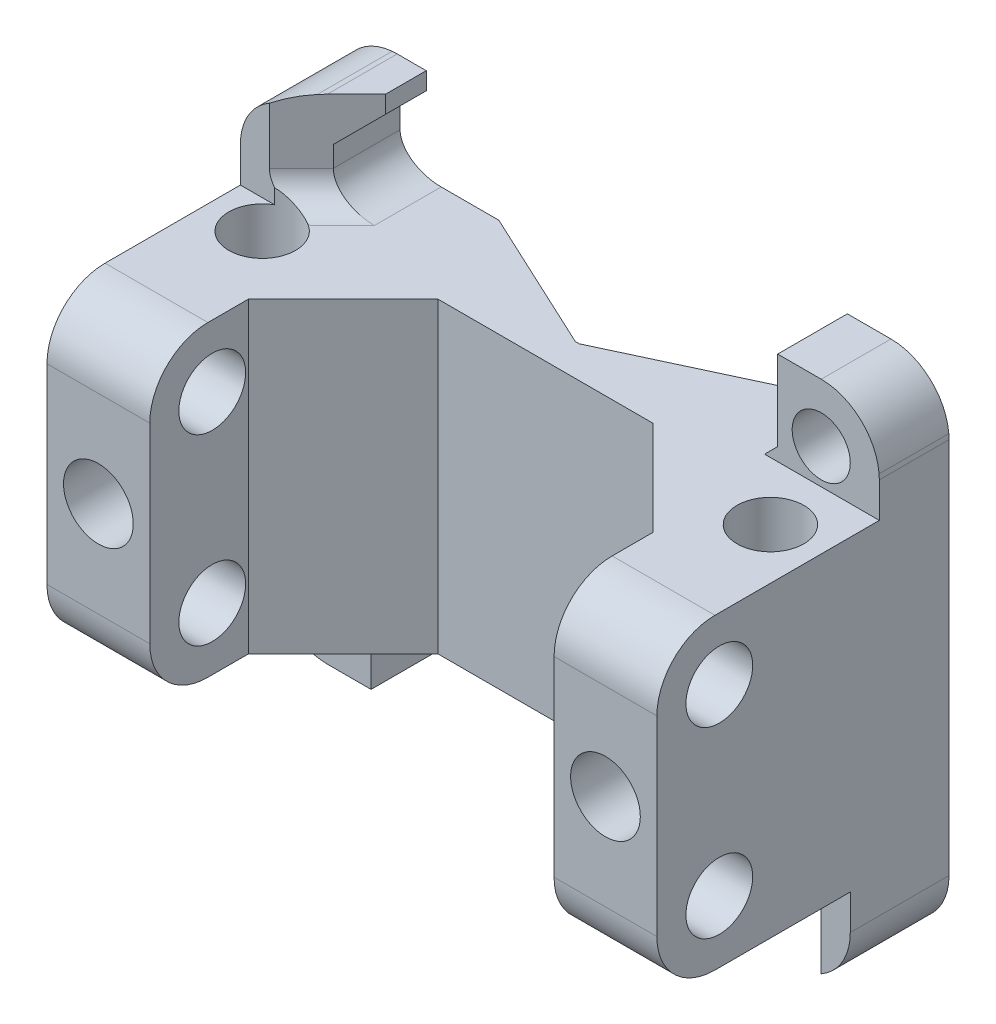
SolidWorks part; units mm, degrees
ref_plane "Top Plane" through (0, 0, 0) normal (0, 0, 1) x (1, 0, 0)
ref_plane "Right Plane" through (0, 0, 0) normal (0, 1, 0) x (1, 0, 0)
ref_plane "Front Plane" through (0, 0, 0) normal (1, 0, 0) x (0, 0, -1)
sketch "Sketch1" plane through (0, 0, 0) normal (0, 0, 1) x (1, 0, 0)
  line L0 (0.6, 14) -> (0.6, 3.577)
  line L3 (20.4, 3) -> (20.4, 13.79)
  line L7 (0, 15) -> (0, 2)
  line L8 (2, 0) -> (19, 0)
  line L9 (19, 0) -> (19.1743, 0.0076)
  line L10 (21, 2) -> (21, 15)
  line L11 (21, 15) -> (20.9924, 15.1743)
  line L12 (19, 17) -> (2, 17)
  line L13 (2, 17) -> (1.8257, 16.9924)
  line L14 (0, 15) -> (0, 2)
  line L15 (2, 0) -> (3.5, 0)
  line L16 (19, 0) -> (19.1743, 0.0076)
  line L17 (21, 2) -> (21, 15)
  line L18 (21, 15) -> (20.9924, 15.1743)
  line L19 (19, 17) -> (17.5, 17)
  line L20 (2, 17) -> (1.8257, 16.9924)
  line L21 (3.5, 0) -> (3.5, 3.577)
  line L22 (3.5, 3.577) -> (0.6, 3.577)
  line L23 (18, 0.6) -> (18, 0)
  line L24 (5.623, 4.077) -> (1.975, 4.077) construction
  line L25 (17.5, 17) -> (17.5, 13.79)
  line L26 (0.6, 15) -> (0.6, 2) construction
  line L27 (2, 0.6) -> (18.9869, 0.6) construction
  line L28 (17.5, 13.79) -> (20.4, 13.79)
  line L29 (19.45, 13.59) -> (19.15, 13.59) construction
  line L30 (20.4, 3) -> (18, 0.6)
  line L31 (20.4, 2) -> (20.4, 14.9869) construction
  line L32 (20.4, 14.9869) -> (20.3936, 15.1339) construction
  line L33 (19, 16.4) -> (2.0131, 16.4) construction
  line L34 (18.9869, 0.6) -> (19.1339, 0.6064) construction
  line L35 (20.4, 3) -> (20.4, 0.6) construction
  line L36 (20.4, 0.6) -> (18, 0.6) construction
  line L37 (2, 0) -> (19, 0) construction
  line L38 (18, 0) -> (19, 0)
  line L39 (20.4, 3) -> (21, 3) construction
  line L40 (2, 0) -> (19, 0) construction
  line L41 (3, 16.4) -> (0.6, 14)
  line L42 (0.6, 14) -> (0.6, 16.4) construction
  line L43 (0.6, 16.4) -> (3, 16.4) construction
  line L44 (3, 16.4) -> (3, 17)
  line L45 (2.0131, 16.4) -> (1.8661, 16.3936) construction
  line L46 (19, 17) -> (2, 17) construction
  line L47 (3, 17) -> (2, 17)
  line L48 (0.6, 14) -> (0, 14) construction
  line L49 (19, 17) -> (2, 17) construction
  arc A4 (0, 2) -> (2, 0) centre (2, 2) ccw
  arc A5 (19.1743, 0.0076) -> (21, 2) centre (19, 2) ccw
  arc A6 (20.9924, 15.1743) -> (19, 17) centre (19, 15) ccw
  arc A7 (1.8257, 16.9924) -> (0, 15) centre (2, 15) ccw
  arc A8 (0, 2) -> (2, 0) centre (2, 2) ccw
  arc A9 (19.1743, 0.0076) -> (21, 2) centre (19, 2) ccw
  arc A10 (20.9924, 15.1743) -> (19, 17) centre (19, 15) ccw
  arc A11 (1.8257, 16.9924) -> (0, 15) centre (2, 15) ccw
  circle A12 centre (2, 2) radius 1 construction
  arc A13 (0.6, 2) -> (2, 0.6) centre (2, 2) ccw construction
  circle A14 centre (19, 15) radius 1 construction
  arc A15 (20.3936, 15.1339) -> (19, 16.4) centre (19, 15) ccw construction
  circle A16 centre (19, 15) radius 1
  circle A17 centre (2, 2) radius 1
  arc A22 (19.1339, 0.6064) -> (20.4, 2) centre (19, 2) ccw construction
  arc A23 (1.8661, 16.3936) -> (0.6, 15) centre (2, 15) ccw construction
  point P42 (19.3, 13.59)
  dimension "D3" = 0.5
  dimension "D4" = 0.5
  dimension "D5" = 0.2
  dimension "D6" = 0.5
  dimension "D7" = 2.4
  dimension "D1" = 0
  dimension "D2" = 0.6
extrude "Boss-Extrude2" add sketch "Sketch1" along normal blind 2.4 contours L16 A9 L17 L18 A10 L19 L25 L28 L3 L30 L23 L38 | L14 A8 L15 L21 L22 L0 L41 L44 L47 L20 A11 | A17 | A16
sketch "Sketch2" plane through (0, 0, 2.4) normal (0, 0, 1) x (1, 0, 0)
  line L0 (3, 13.79) -> (21, 13.79)
  line L1 (18, 0) -> (18, 3.21)
  line L2 (3, 13.79) -> (3, 17)
  line L5 (0, 15) -> (0, 2) construction
  line L6 (18, 3.21) -> (0, 3.21)
  line L7 (0, 15) -> (0, 2)
  line L8 (2, 0) -> (19, 0)
  line L9 (19, 0) -> (19.1743, 0.0076)
  line L10 (21, 2) -> (21, 15)
  line L11 (21, 15) -> (20.9924, 15.1743)
  line L12 (19, 17) -> (2, 17)
  line L13 (2, 17) -> (1.8257, 16.9924)
  line L14 (0, 15) -> (0, 3.21)
  line L15 (18, 0) -> (19, 0)
  line L16 (19, 0) -> (19.1743, 0.0076)
  line L17 (21, 2) -> (21, 13.79)
  line L19 (3, 17) -> (2, 17)
  line L20 (2, 17) -> (1.8257, 16.9924)
  line L22 (17.5, 13.79) -> (20.4, 13.79) construction
  arc A4 (0, 2) -> (2, 0) centre (2, 2) ccw
  arc A5 (19.1743, 0.0076) -> (21, 2) centre (19, 2) ccw
  arc A6 (20.9924, 15.1743) -> (19, 17) centre (19, 15) ccw
  arc A7 (1.8257, 16.9924) -> (0, 15) centre (2, 15) ccw
  arc A9 (19.1743, 0.0076) -> (21, 2) centre (19, 2) ccw
  arc A11 (1.8257, 16.9924) -> (0, 15) centre (2, 15) ccw
  dimension "D1" = 0
extrude "Boss-Extrude5" add sketch "Sketch2" against normal blind 0.1 and the other way blind 1
chamfer "Chamfer1" distance 2 angle 45 2 edges at (18, 1.605, 3.4) (3, 15.395, 3.4)
fillet "Fillet1" radius 1 2 edges at (19.45, 3.21, 2.85) (1.55, 13.79, 2.85)
sketch "Sketch3" plane through (0, 13.79, 0) normal (0, 1, 0) x (1, 0, 0)
  line L0 (21, -3.4) -> (2.4142, -3.4) construction
  line L1 (21, -4.4) -> (17.5, -4.4) construction
  line L2 (21, -4.4) -> (21, -3.4)
  line L3 (21, -3.4) -> (19.8179, -3.4)
  line L4 (17.5, -4.4) -> (17.5, -3.4)
  line L5 (17.5, -2.4) -> (17.5, -3.4) construction
  line L6 (18.6821, -3.4) -> (17.5, -3.4)
  arc A0 (18.6821, -3.4) -> (19.8179, -3.4) centre (19.25, -4.4) ccw
  arc A1 (21, -4.4) -> (17.5, -4.4) centre (19.25, -4.4) cw
  dimension "D1" = 0.6
  dimension "D2" = 1
extrude "Boss-Extrude6" add sketch "Sketch3" against normal up to surface (10.58 mm away) up to face at (7.1786, 3.21, 2.7)
ref_plane "Plane1" through (10.5, 0, 0) normal (-1, 0, 0) x (0, 0, 1)
sketch "Sketch9" plane through (0, 13.79, 0) normal (0, 1, 0) x (1, 0, 0)
  circle A0 centre (19.25, -4.4) radius 1.15
  arc A1 (18.6821, -3.4) -> (19.8179, -3.4) centre (19.25, -4.4) ccw construction
extrude "Cut-Extrude5" cut sketch "Sketch9" against normal through all both and the other way through all
sketch "Sketch10" plane through (0, 13.79, 0) normal (0, 1, 0) x (1, 0, 0)
  line L1 (17.5, -6.6594) -> (17.5, -4.4)
  line L2 (17.5, -4.4) -> (18.1, -4.4)
  line L3 (20.4, -4.4) -> (21, -4.4)
  line L4 (21, -4.4) -> (21, -6.6594)
  line L5 (21, -6.6594) -> (17.5, -6.6594)
  circle A1 centre (19.25, -4.4) radius 1.15 construction
  arc A2 (18.1, -4.4) -> (20.4, -4.4) centre (19.25, -4.4) ccw
  dimension "D1" = 1.1094
extrude "Boss-Extrude10" add sketch "Sketch10" against normal up to surface (10.58 mm away) up to face at (13.2143, 3.21, 3.5417)
chamfer "Chamfer4" distance 3.3 angle 45 1 edges at (17.5, 8.5, 3.4)
sketch "Sketch12" plane through (21, 0, 0) normal (1, 0, 0) x (0, 0, -1)
  line L0 (-6.6594, 5.35) -> (-10.0594, 5.35) construction
  line L1 (-6.6594, 3.21) -> (-10.0594, 3.21)
  line L2 (-6.6594, 3.21) -> (-6.6594, 13.79)
  line L3 (-6.6594, 13.79) -> (-10.0594, 13.79)
  line L4 (-10.0594, 3.21) -> (-10.0594, 13.79)
  line L5 (-6.6594, 8.5) -> (-10.0594, 8.5) construction
  circle A0 centre (-7.9094, 5.35) radius 1.15
  circle A1 centre (-7.9094, 11.65) radius 1.15
  dimension "D1" = 2.3
  dimension "D2" = 1
  dimension "D4" = 4
  dimension "D3" = 0.1
extrude "Boss-Extrude11" add sketch "Sketch12" against normal blind 3.54
fillet "Fillet2" radius 2 2 edges at (19.23, 3.21, 10.0594) (19.23, 13.79, 10.0594)
sketch "Sketch13" plane through (0, 0, 10.0594) normal (0, 0, 1) x (1, 0, 0)
  line L0 (21, 8.5) -> (17.46, 8.5) construction
  line L1 (21, 11.79) -> (21, 5.21) construction
  line L2 (17.46, 11.79) -> (17.46, 5.21) construction
  circle A0 centre (19.23, 8.5) radius 1.2
  point P8 (19.23, 8.5)
  dimension "D1" = 2.4
extrude "Cut-Extrude7" cut sketch "Sketch13" against normal blind 5.5
mirror "Mirror1" about plane through (10.5, 0, 0) normal (-1, 0, 0) of "Cut-Extrude7", "Chamfer4", "Boss-Extrude6", "Cut-Extrude5", "Boss-Extrude10", "Boss-Extrude11", "Fillet2"
ref_plane "Plane2" through (0, 8.5, 0) normal (0, 1, 0) x (1, 0, 0)
chamfer "Chamfer3" distance 1 angle 45 2 edges at (20.4, 13.79, 1.15) (0.6, 3.577, 1.15)
sketch "Sketch6" plane through (0, 0, 2.3) normal (0, 0, -1) x (-1, 0, 0)
  line L0 (-3.5, 3.21) -> (-17.4858, 3.21) construction
  line L1 (0, 3.21) -> (-17.4858, 3.21)
  line L2 (0, 3.21) -> (0, 3.81)
  line L3 (0, 3.81) -> (-17.4858, 3.81)
  line L6 (-17.5, 13.79) -> (-3.5142, 13.79)
  line L7 (-21, 13.89) -> (-21, 13.19)
  line L8 (-21, 13.19) -> (-0.5, 13.19)
  line L9 (-0.5, 15.5) -> (-0.5, 13.19)
  line L12 (-10.5, 14.28) -> (-10.5, 13.79) construction
  line L13 (-4.1902, 14.28) -> (-16.8098, 14.28) construction
  line L14 (-21, 3.674) -> (-17.8, 3.674)
  line L18 (-20.4, 3) -> (-18.9, 1.5) construction
  line L19 (-20.4, 3) -> (-20.4, 12.79) construction
  line L20 (-17.4858, 3.21) -> (-17.4858, 3.81)
  line L22 (-21, 3.674) -> (-20.4, 3)
  line L23 (-18.9, 1.5) -> (-18.9, 2.21)
  line L24 (-2.1, 14.79) -> (-2.1, 15.5)
  line L25 (-2.1, 15.5) -> (-0.5, 15.5)
  line L26 (-17.5, 13.79) -> (-3.5142, 13.79) construction
  line L27 (-18.9, 1.5) -> (-20.4, 1.5)
  line L28 (-20.4, 1.5) -> (-20.4, 3)
  line L29 (-17.4858, 3.81) -> (-17.8, 3.674)
  line L30 (-17.924, 3.774) -> (-18.176, 3.774) construction
  line L31 (-17.9, 3.774) -> (-17.9, 4.426) construction
  line L32 (0, 15) -> (0, 2) construction
  line L33 (-21, 2) -> (-21, 15) construction
  line L34 (-17.5, 13.79) -> (-17.5, 13.89)
  line L35 (-17.5, 17) -> (-17.5, 13.79) construction
  line L36 (-17.5, 13.89) -> (-21, 13.89)
  line L39 (-10.5, 13.79) -> (-10.5, 13.19) construction
  line L40 (-11.5185, 3.21) -> (-11.5185, 3.81) construction
  line L41 (-0.6, 14) -> (-0.6, 4.577) construction
  arc A0 (-18.9, 2.21) -> (-17.4858, 3.21) centre (-17.8393, 2.21) cw
  ellipse E0 centre (-17.4858, 2.21) end of major axis (-18.9, 2.21) minor radius 1 (-17.4858, 3.21) -> (-18.9, 2.21) ccw construction
  ellipse E1 centre (-3.5142, 14.79) end of major axis (-2.1, 14.79) minor radius 1 (-3.5142, 13.79) -> (-2.1, 14.79) ccw construction
  ellipse E2 centre (-3.5142, 14.79) end of major axis (-2.1, 14.79) minor radius 1 (-3.5142, 13.79) -> (-2.1, 14.79) ccw
  line M19 (-17.5, 13.79) -> (-19.4, 13.79)
  line M20 (-19.4, 13.79) -> (-20.4, 12.79)
  line M21 (-20.4, 12.79) -> (-20.4, 3)
  line M22 (-20.4, 3) -> (-18.9, 1.5)
  line M23 (-18.9, 1.5) -> (-18.9, 2.21)
  ellipse M24 centre (-17.4858, 2.21) end of major axis (-18.9, 2.21) minor radius 1 (-18.9, 2.21) -> (-17.4858, 3.21) cw
  line M25 (-17.4858, 3.21) -> (-3.5, 3.21)
  line M26 (-3.5, 3.577) -> (-1.6, 3.577)
  line M27 (-1.6, 3.577) -> (-0.6, 4.577)
  line M28 (-0.6, 4.577) -> (-0.6, 14)
  line M29 (-0.6, 14) -> (-2.1, 15.5)
  line M30 (-2.1, 15.5) -> (-2.1, 14.79)
  ellipse M31 centre (-3.5142, 14.79) end of major axis (-2.1, 14.79) minor radius 1 (-2.1, 14.79) -> (-3.5142, 13.79) cw
  line M32 (-3.5142, 13.79) -> (-17.5, 13.79)
  dimension "D1" = 0.1
  dimension "D2" = 0.6
  dimension "D3" = 0.1
  dimension "D4" = 0.1
  dimension "D5" = 0.1
extrude "Boss-Extrude8" add sketch "Sketch6" along normal up to surface (2.3 mm away) contours A0 L20 L29 L14 M23 M24 M21 M22 | L28 L27 M22 | L14 L22 M21 | L2 L3 L1 M27 M26 M25 M24 | L20 L3 M25 M26 M27 | L25 L8 L9 M29 M28 | L8 M20 M28 M29 M30 M31 M32 M19 | L34 L36 L7 L8 M20 M19 region at (8.7429, 3.51, 2.3) region at (19.1765, 3.0245, 2.3) region at (19.9, 2, 2.3) region at (1.0063, 14.8884, 2.3) region at (9.0345, 13.5964, 2.3) region at (20.6, 3.4493, 2.3) region at (20.0013, 13.6143, 2.3) up to face at (1.7353, 9.172, 0)
sketch "Sketch7" plane through (0, 0, 0) normal (0, 0, -1) x (-1, 0, 0)
  line L0 (-0.6, 13.19) -> (-20, 13.19) construction
  line L1 (-17.65, 13.19) -> (-19.65, 13.19)
  line L2 (-17.65, 13.19) -> (-17.65, 13.79)
  line L3 (-17.65, 13.79) -> (-19.65, 13.79)
  line L4 (-19.65, 13.19) -> (-19.65, 13.79)
  line L5 (-17.85, 13.59) -> (-17.85, 12.79) construction
  line L6 (-17.85, 13.59) -> (-19.45, 13.59) construction
  line L7 (-19.45, 13.59) -> (-18.65, 13.79) construction
  line L8 (-18.65, 13.79) -> (-18.65, 13.589) construction
  line L9 (-17.65, 13.59) -> (-17.85, 13.59) construction
  line L10 (-17.85, 13.59) -> (-17.85, 13.79) construction
  dimension "D1" = 0.2
extrude "Cut-Extrude4" cut sketch "Sketch7" against normal blind 1
sketch "Sketch11" plane through (0, 0, 0) normal (0, 0, -1) x (-1, 0, 0)
  line L0 (-3.5, 3.21) -> (-17.4858, 3.21) construction
  line L1 (-5.5, 3.21) -> (-15.5, 3.21)
  line L2 (-5.5, 3.21) -> (-5.5, 3.81)
  line L3 (-5.5, 3.81) -> (-15.5, 3.81)
  line L4 (-15.5, 3.21) -> (-15.5, 3.81)
  line L5 (-17.4858, 3.81) -> (-1.367, 3.81) construction
  line L6 (0, 8.5) -> (-21, 8.5) construction
  line L7 (0, 15) -> (0, 2) construction
  line L8 (-21, 2) -> (-21, 15) construction
  line L9 (-10.5, 3.81) -> (-10.5, 8.5) construction
  line L10 (-0.6, 13.19) -> (-17.65, 13.19) construction
  line L11 (-5.5, 13.19) -> (-15.5, 13.19)
  line L12 (-5.5, 13.19) -> (-5.5, 13.79)
  line L13 (-5.5, 13.79) -> (-15.5, 13.79)
  line L14 (-15.5, 13.19) -> (-15.5, 13.79)
  line L15 (-17.5, 13.79) -> (-3.5142, 13.79) construction
  dimension "D1" = 10
extrude "Cut-Extrude6" cut sketch "Sketch11" against normal up to surface (2.3 mm away) up to face at (12.3316, 7.3394, 2.3)
chamfer "Chamfer5" distance 2.3 angle 65 4 edges at (15.5, 3.51, 2.3) (5.5, 3.51, 2.3) (15.5, 13.49, 2.3) (5.5, 13.49, 2.3) first distance on face at (15.5, 3.51, 1.15) first distance on face at (5.5, 3.51, 1.15) first distance on face at (15.5, 13.49, 1.15) first distance on face at (5.5, 13.49, 1.15)
chamfer "Chamfer6" distance 0.45 angle 45 1 edges at (17.5, 13.79, 1.2)
equation "\".42.03381288mm\"=2.03381"
